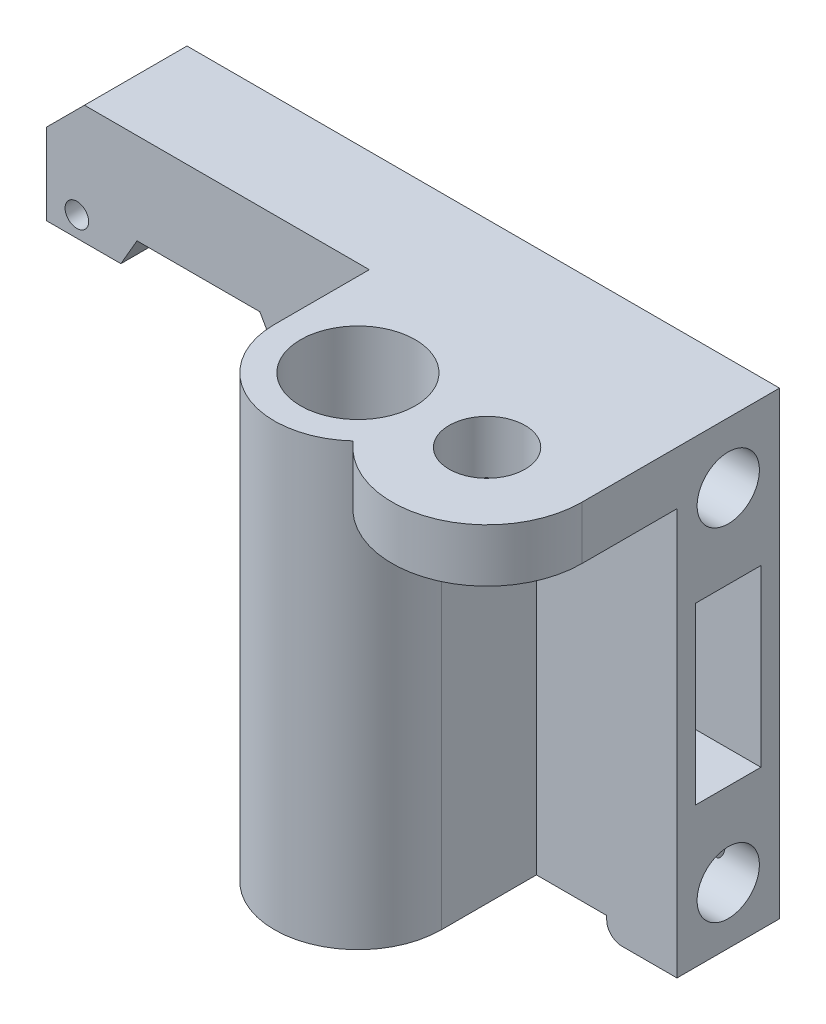
SolidWorks part; units mm, degrees
ref_plane "Alzado" through (0, 0, 0) normal (0, 0, 1) x (1, 0, 0)
ref_plane "Planta" through (0, 0, 0) normal (0, 1, 0) x (1, 0, 0)
ref_plane "Vista lateral" through (0, 0, 0) normal (1, 0, 0) x (0, 0, -1)
sketch "Croquis1" plane through (0, 0, 0) normal (0, 1, 0) x (1, 0, 0)
  line L0 (-11, 0) -> (-11, 12.5)
  line L2 (29.5, 0) -> (29.5, 8)
  line L4 (29.5, 8) -> (29.5, 26)
  line L5 (29.5, 26) -> (-53.5, 26)
  line L6 (-53.5, 26) -> (-53.5, 12.5)
  line L7 (-11, 12.5) -> (-53.5, 12.5)
  arc A0 (-11, 0) -> (7.4632, -8.0808) centre (0, 0) ccw
  arc A1 (7.4632, -8.0808) -> (29.5, 0) centre (17, 0) ccw
  circle A4 centre (0, 0) radius 7.55
  circle A5 centre (17, 0) radius 5
  dimension "D2" = 15.1
  dimension "D3" = 10
  dimension "D4" = 11
  dimension "D5" = 12.5
  dimension "D1" = 17
  dimension "D6" = 18
  dimension "D7" = 83
  dimension "D8" = 26
  dimension "D9" = 12.5
  dimension "D10" = 29.5
  dimension "D11" = 12.5
extrude "Saliente-Extruir1" add sketch "Croquis1" along normal blind 7
sketch "Croquis2" plane through (0, 0, 0) normal (0, -1, 0) x (1, 0, 0)
  line L0 (29.5, 0) -> (29.5, -26) construction
  line L1 (29.5, -26) -> (-53.5, -26) construction
  line L2 (-53.5, -12.5) -> (-11, -12.5) construction
  line L3 (-53.5, -26) -> (-53.5, -12.5) construction
  line L4 (29.5, 0) -> (29.5, -26)
  line L5 (29.5, -26) -> (-53.5, -26)
  line L6 (-53.5, -12.5) -> (-11, -12.5)
  line L7 (-53.5, -26) -> (-53.5, -12.5)
  line L8 (-11, -12.5) -> (29.5, -12.5)
  line M3 (-11, -12.5) -> (-53.5, -12.5)
  line M4 (-53.5, -12.5) -> (-53.5, -26)
  line M5 (-53.5, -26) -> (29.5, -26)
  line M6 (29.5, -26) -> (29.5, 0)
extrude "Saliente-Extruir2" add sketch "Croquis2" along normal blind 51 contours L8 M3 M4 M5 M6 region at (-12, 0, -19.25)
sketch "Croquis3" plane through (0, 0, 0) normal (0, -1, 0) x (1, 0, 0)
  line L0 (-11, -12.5) -> (29.5, -12.5) construction
  line L1 (-11, -12.5) -> (-11, 0) construction
  line L2 (-11, -12.5) -> (11, -12.5)
  line L3 (-11, -12.5) -> (-11, 0)
  line L4 (11, 0) -> (11, -12.5)
  circle A0 centre (0, 0) radius 7.55 construction
  arc A1 (7.4632, 8.0808) -> (-11, 0) centre (0, 0) ccw construction
  circle A2 centre (0, 0) radius 7.55
  arc A3 (7.4632, 8.0808) -> (-11, 0) centre (0, 0) ccw
  arc A4 (11, 0) -> (-11, 0) centre (0, 0) ccw
  line M1 (-11, 0) -> (-11, -12.5)
  line M2 (-11, -12.5) -> (29.5, -12.5)
  arc M5 (7.4632, 8.0808) -> (-11, 0) centre (0, 0) ccw
  circle M6 centre (0, 0) radius 7.55
extrude "Saliente-Extruir3" add sketch "Croquis3" along normal blind 51 contours L4 A4 M5 M1 M2 M6 region at (-10.6781, 0, -6.25)
sketch "Croquis5" plane through (0, 0, -12.5) normal (0, 0, 1) x (1, 0, 0)
  line L0 (-53.5, 7) -> (-11, 7) construction
  line L1 (-53.5, 7) -> (-53.5, -51) construction
  line L2 (-53.5, 7) -> (-48.5, 7)
  line L3 (-53.5, 7) -> (-53.5, 2)
  line L4 (-53.5, 2) -> (-48.5, 7)
  dimension "D1" = 5
  dimension "D2" = 5
extrude "Cortar-Extruir2" cut sketch "Croquis5" against normal through all
sketch "Croquis7" plane through (29.5, 0, 0) normal (1, 0, 0) x (0, 0, -1)
  line L0 (0, 7) -> (26, 7) construction
  line L1 (26, 7) -> (26, -51) construction
  circle A0 centre (19.25, -1) radius 4.1
  circle A1 centre (19.25, -46) radius 4.1
  dimension "D1" = 8.2
  dimension "D2" = 8.2
  dimension "D3" = 45
  dimension "D4" = 8
  dimension "D5" = 6.75
extrude "Cortar-Extruir3" cut sketch "Croquis7" against normal blind 35
sketch "Croquis8" plane through (29.5, 0, 0) normal (1, 0, 0) x (0, 0, -1)
  line L0 (12.5, -51) -> (12.5, 0) construction
  line L1 (14.95, -12) -> (23.55, -12)
  line L2 (14.95, -12) -> (14.95, -35)
  line L3 (14.95, -35) -> (23.55, -35)
  line L4 (23.55, -12) -> (23.55, -35)
  line L5 (14.95, -12) -> (23.55, -35) construction
  line L6 (14.95, -35) -> (23.55, -12) construction
  circle A0 centre (19.25, -1) radius 4.1 construction
  point P0 (19.25, -23.5)
  dimension "D1" = 8.6
  dimension "D2" = 23
  dimension "D3" = 6.75
  dimension "D4" = 22.5
extrude "Cortar-Extruir4" cut sketch "Croquis8" against normal through all
sketch "Croquis10" plane through (0, 0, -12.5) normal (0, 0, 1) x (1, 0, 0)
  line L0 (-53.5, 2) -> (-53.5, -51) construction
  line L1 (-48.5, 7) -> (-11, 7) construction
  circle A0 centre (-49.5, -6) radius 1.55
  circle A1 centre (-18.5, -6) radius 1.55
  circle A2 centre (-18.5, -37) radius 1.55
  circle A3 centre (-34, -21.5) radius 11 construction
  point P9 (-53.5, -24.5)
  dimension "D3" = 3.1
  dimension "D4" = 3.1
  dimension "D5" = 3.1
  dimension "D8" = 22
  dimension "D1" = 31
  dimension "D2" = 31
  dimension "D6" = 4
  dimension "D7" = 13
  dimension "D9" = 15.5
  dimension "D10" = 15.5
extrude "Cortar-Extruir7" cut sketch "Croquis10" against normal through all
sketch "Croquis11" plane through (0, 0, -12.5) normal (0, 0, 1) x (1, 0, 0)
  line L0 (-53.5, 2) -> (-53.5, -51) construction
  line L1 (-53.5, -8.6693) -> (-53.5, -51)
  line L2 (-53.5, -8.6693) -> (-43.7014, -8.6693)
  line L4 (-25.4171, -33) -> (-17.3342, -19)
  line L5 (-17.3342, -19) -> (-25.4171, -5)
  line L6 (-25.4171, -5) -> (-41.5829, -5)
  line L7 (-41.5829, -5) -> (-43.7014, -8.6693)
  line L8 (-25.4171, -33) -> (-25.4171, -51)
  line L9 (-25.4171, -51) -> (-53.5, -51)
  line L10 (-53.5, -51) -> (-53.5, -8.6693)
  line L11 (-49.6658, -19) -> (-45.6244, -26) [skipped]
  line L12 (-41.5829, -33) -> (-25.4171, -33) [skipped]
  arc A0 (-21.3756, -26) -> (-33.5, -5) centre (-33.5, -19) ccw construction
  line M9 (-53.5, 2) -> (-53.5, -51)
  dimension "D1" = 28
  dimension "D2" = 20
  dimension "D3" = 32
  dimension "D4" = 9.7986
  dimension "D5" = 18
  dimension "D6" = 28.0829
extrude "Cortar-Extruir8" cut sketch "Croquis11" against normal through all contours L9 L8 L4 L5 L6 L7 L2 M9 region at (-37.8204, -27.8734, -12.5)
sketch "Croquis12" plane through (0, 0, -12.5) normal (0, 0, 1) x (1, 0, 0)
  line L0 (-25.4171, -51) -> (-25.4171, -46)
  line L1 (-25.4171, -33) -> (-25.4171, -51) construction
  line L2 (-25.4171, -46) -> (-11, -46)
  line L3 (-11, 7) -> (-11, -51) construction
  line L4 (-11, -46) -> (-11, -51)
  line L5 (-25.4171, -51) -> (-11, -51) construction
  line L6 (-11, -51) -> (-25.4171, -51)
  dimension "D1" = 5
extrude "Cortar-Extruir9" cut sketch "Croquis12" against normal through all
sketch "Croquis13" plane through (0, -51, 0) normal (0, -1, 0) x (1, 0, 0)
  line L0 (29.5, -12.5) -> (20.25, -12.5)
  line L1 (11, -12.5) -> (29.5, -12.5) construction
  line L2 (20.25, -12.5) -> (20.25, -26)
  line L3 (-11, -26) -> (29.5, -26) construction
  line L4 (20.25, -26) -> (29.5, -26)
  line L5 (29.5, -26) -> (29.5, -12.5)
extrude "Saliente-Extruir4" add sketch "Croquis13" along normal blind 2.5
fillet "Redondeo2" radius 2 1 edges at (20.25, -53.5, -19.25) type face fillet first side face at (24.875, -53.5, -19.25) second side face at (20.25, -52.25, -19.25)
sketch "Croquis14" plane through (0, -53.5, 0) normal (0, -1, 0) x (1, 0, 0)
  line L0 (29.5, -12.5) -> (22.25, -12.5) construction
  line L1 (22.25, -12.5) -> (22.25, -26) construction
  circle A0 centre (24.25, -14) radius 1
  circle A1 centre (24.25, -24) radius 1
  dimension "D1" = 2
  dimension "D2" = 2
  dimension "D3" = 10
  dimension "D4" = 1.5
  dimension "D5" = 2
extrude "Cortar-Extruir10" cut sketch "Croquis14" against normal blind 8
